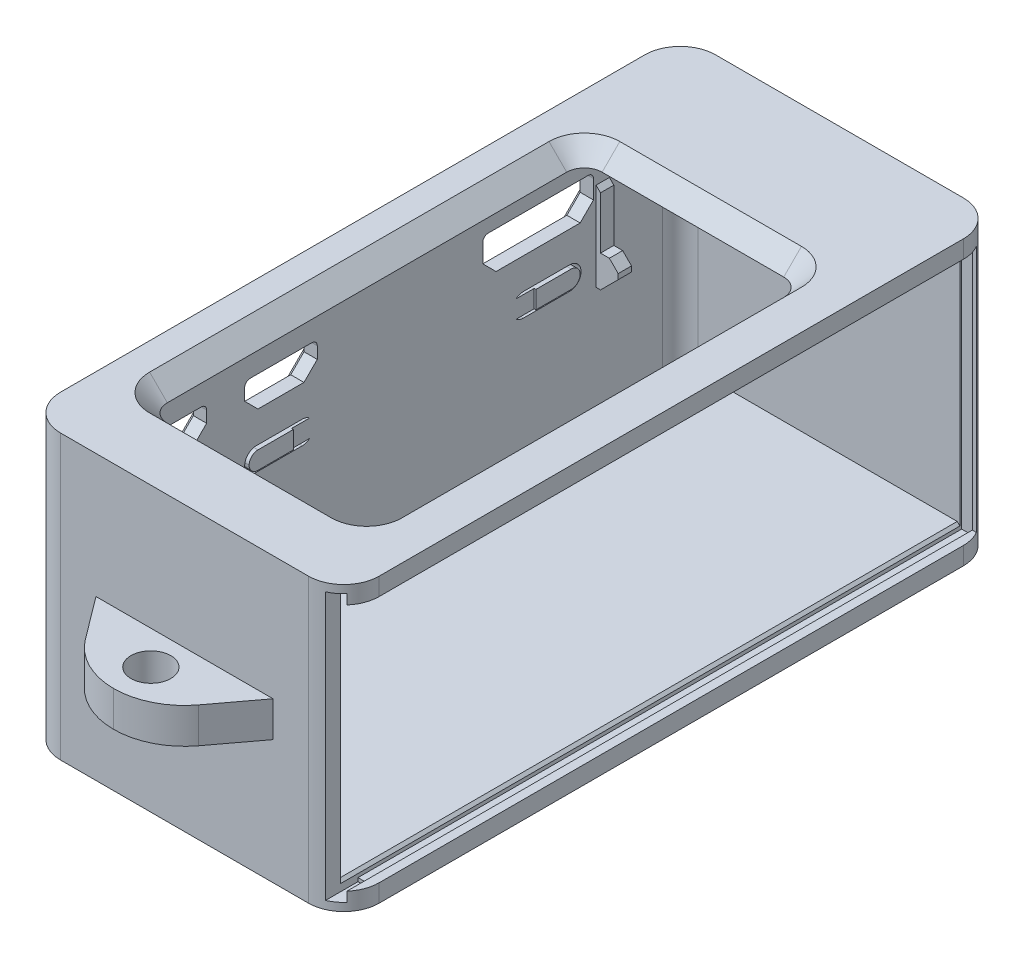
SolidWorks part; units mm, degrees
ref_plane "前视基准面" through (0, 0, 0) normal (0, 0, 1) x (1, 0, 0)
ref_plane "上视基准面" through (0, 0, 0) normal (0, 1, 0) x (1, 0, 0)
ref_plane "右视基准面" through (0, 0, 0) normal (1, 0, 0) x (0, 0, -1)
sketch "草图1" plane through (0, 0, 0) normal (1, 0, 0) x (0, 0, -1)
  line L1 (-54.0501, 29.0398) -> (19.9499, 29.0398)
  line L2 (-54.0501, 29.0398) -> (-54.0501, -2.9602)
  line L3 (-54.0501, -2.9602) -> (19.9499, -2.9602)
  line L4 (19.9499, 29.0398) -> (19.9499, -2.9602)
  dimension "D1" = 74
  dimension "D2" = 32
extrude "凸台-拉伸1" add sketch "草图1" along normal blind 36
sketch "草图2" plane through (36, 0, 0) normal (1, 0, 0) x (0, 0, -1)
  line L8 (17.9499, -0.9602) -> (17.9499, 27.0398)
  line L9 (-52.0501, -0.9602) -> (17.9499, -0.9602)
  line L10 (-52.0501, 27.0398) -> (-52.0501, -0.9602)
  line L11 (17.9499, 27.0398) -> (-52.0501, 27.0398)
  line L12 (17.9499, -0.9602) -> (17.9499, 27.0398)
  line L13 (-52.0501, -0.9602) -> (17.9499, -0.9602)
  line L14 (-52.0501, 27.0398) -> (-52.0501, -0.9602)
  line L15 (17.9499, 27.0398) -> (-52.0501, 27.0398)
  dimension "D1" = 2
extrude "切除-拉伸1" cut sketch "草图2" against normal blind 34
fillet "圆角1" radius 2 2 edges at (2, 13.0398, -17.9499) (2, 13.0398, 52.0501)
fillet "圆角2" radius 4 4 edges at (0, 13.0398, -19.9499) (0, 13.0398, 54.0501) (36, 13.0398, 54.0501) (36, 13.0398, -19.9499)
sketch "草图3" plane through (0, 29.0398, 0) normal (0, 1, 0) x (1, 0, 0)
  line L0 (32, 19.9499) -> (4, 19.9499) construction
  line L1 (29.59, 4.0599) -> (5.07, 4.0599)
  line L2 (29.59, 4.0599) -> (29.59, -45.0601)
  line L3 (29.59, -45.0601) -> (5.07, -45.0601)
  line L4 (5.07, 4.0599) -> (5.07, -45.0601)
  line L5 (36, 15.9499) -> (36, -50.0501) construction
  line L6 (32, -54.0501) -> (4, -54.0501) construction
  line L7 (0, 15.9499) -> (0, -50.0501) construction
  dimension "D1" = 15.89
  dimension "D2" = 6.41
  dimension "D3" = 8.99
  dimension "D4" = 5.07
extrude "切除-拉伸2" cut sketch "草图3" against normal blind 10
fillet "圆角3" radius 2 4 edges at (5.07, 28.0398, 45.0601) (29.59, 28.0398, 45.0601) (29.59, 28.0398, -4.0599) (5.07, 28.0398, -4.0599)
chamfer "倒角1" distance 2 angle 45 8 edges at (17.33, 29.0398, 45.0601) (29.0042, 29.0398, 44.4744) (5.6558, 29.0398, 44.4744) (29.59, 29.0398, 20.5001) (5.07, 29.0398, 20.5001) (29.0042, 29.0398, -3.4741) (5.6558, 29.0398, -3.4741) (17.33, 29.0398, -4.0599)
sketch "草图4" plane through (0, 0, 0) normal (-1, 0, 0) x (0, 0, 1)
  line L0 (-15.9499, 29.0398) -> (50.0501, 29.0398) construction
  line L1 (-8.1499, 22.4398) -> (4.3501, 22.4398)
  line L2 (-8.1499, 22.4398) -> (-8.1499, 18.2398)
  line L3 (-8.1499, 18.2398) -> (4.3501, 18.2398)
  line L4 (4.3501, 22.4398) -> (4.3501, 18.2398)
  line L5 (23.0501, 21.6812) -> (31.2501, 21.6812)
  line L6 (23.0501, 21.6812) -> (23.0501, 18.2398)
  line L7 (23.0501, 18.2398) -> (31.2501, 18.2398)
  line L8 (31.2501, 21.6812) -> (31.2501, 18.2398)
  line L9 (35.5501, 21.6398) -> (43.7501, 21.6398)
  line L10 (35.5501, 21.6398) -> (35.5501, 18.2398)
  line L11 (35.5501, 18.2398) -> (43.7501, 18.2398)
  line L12 (43.7501, 21.6398) -> (43.7501, 18.2398)
  line L13 (-6.7499, 14.7398) -> (1.0501, 14.7398)
  line L14 (-6.7499, 14.7398) -> (-6.7499, 12.1398)
  line L15 (-6.7499, 12.1398) -> (1.0501, 12.1398)
  line L16 (1.0501, 14.7398) -> (1.0501, 12.1398)
  line L17 (23.4501, 14.7398) -> (31.2501, 14.7398)
  line L18 (23.4501, 14.7398) -> (23.4501, 12.1398)
  line L19 (23.4501, 12.1398) -> (31.2501, 12.1398)
  line L20 (31.2501, 14.7398) -> (31.2501, 12.1398)
  line L21 (33.8696, 14.7398) -> (43.3696, 14.7398)
  line L22 (33.8696, 14.7398) -> (33.8696, 11.5398)
  line L23 (33.8696, 11.5398) -> (43.3696, 11.5398)
  line L24 (43.3696, 14.7398) -> (43.3696, 11.5398)
  line L25 (54.0501, 29.0398) -> (54.0501, -2.9602) construction
  point P24 (0, 0)
  point P27 (0, 0)
  point P28 (0, 0)
  point P31 (0, 0)
  point P32 (0, 0)
  dimension "D1" = 14.3
  dimension "D2" = 3.2
  dimension "D3" = 2.6
  dimension "D4" = 7.8
  dimension "D5" = 7.8
  dimension "D6" = 8.2
  dimension "D7" = 8.2
  dimension "D8" = 3.4
  dimension "D9" = 12.5
  dimension "D10" = 4.2
  dimension "D11" = 10.8
  dimension "D12" = 10.3
  dimension "D13" = 4.3
  dimension "D14" = 18.7
  dimension "D15" = 9.5
  dimension "D16" = 53
extrude "切除-拉伸3" cut sketch "草图4" against normal blind 10
sketch "草图5" plane through (2, 0, 0) normal (1, 0, 0) x (0, 0, -1)
  line L0 (-23.4501, 12.1398) -> (-23.4501, 14.7398) construction
  line L1 (-23.4501, 14.4398) -> (-30.9501, 14.4398)
  line L2 (-23.4501, 14.4398) -> (-23.4501, 12.4398)
  line L3 (-23.4501, 12.4398) -> (-30.9501, 12.4398)
  line L4 (-30.9501, 14.4398) -> (-30.9501, 12.4398)
  line L5 (-1.0501, 14.7398) -> (-1.0501, 12.1398) construction
  line L6 (-1.0501, 12.4398) -> (6.4499, 12.4398)
  line L7 (-1.0501, 12.4398) -> (-1.0501, 14.4398)
  line L8 (-1.0501, 14.4398) -> (6.4499, 14.4398)
  line L9 (6.4499, 12.4398) -> (6.4499, 14.4398)
  line L10 (-23.4501, 14.7398) -> (-31.2501, 14.7398) construction
  line L11 (-31.2501, 12.1398) -> (-23.4501, 12.1398) construction
  line L12 (-31.2501, 14.7398) -> (-31.2501, 12.1398) construction
  line L13 (6.7499, 14.7398) -> (-1.0501, 14.7398) construction
  line L14 (-1.0501, 12.1398) -> (6.7499, 12.1398) construction
  line L15 (6.7499, 12.1398) -> (6.7499, 14.7398) construction
  dimension "D1" = 0.3
  dimension "D2" = 0.3
  dimension "D3" = 0.3
  dimension "D4" = 0.3
  dimension "D5" = 0.3
  dimension "D6" = 0.3
extrude "凸台-拉伸2" add sketch "草图5" against normal blind 1.2
sketch "草图6" plane through (0.8, 0, 0) normal (-1, 0, 0) x (0, 0, 1)
  line L0 (1.0501, 12.4398) -> (-6.4499, 12.4398) construction
  line L1 (-6.4499, 14.4398) -> (-1.4499, 14.4398)
  line L2 (-6.4499, 14.4398) -> (-6.4499, 12.4398)
  line L3 (-6.4499, 12.4398) -> (-1.4499, 12.4398)
  line L4 (-1.4499, 14.4398) -> (-1.4499, 12.4398)
  line L5 (30.9501, 12.4398) -> (23.4501, 12.4398) construction
  line L6 (30.9501, 14.4398) -> (25.9501, 14.4398)
  line L7 (30.9501, 14.4398) -> (30.9501, 12.4398)
  line L8 (30.9501, 12.4398) -> (25.9501, 12.4398)
  line L9 (25.9501, 14.4398) -> (25.9501, 12.4398)
  dimension "D1" = 5
  dimension "D2" = 5
extrude "凸台-拉伸3" add sketch "草图6" along normal blind 1.5 and the other way blind 1.4
fillet "圆角4" radius 0.6 10 edges at (1, 11.5398, 33.8696) (1, 14.7398, 33.8696) (1, 14.7398, 43.3696) (1, 11.5398, 43.3696) (1, 21.6398, 35.5501) (1, 21.6398, 43.7501) (1, 21.6812, 31.2501) (1, 21.6812, 23.0501) (1, 22.4398, -8.1499) (1, 22.4398, 4.3501)
chamfer "倒角2" distance 1.5 angle 45 6 edges at (1, 18.2398, 43.7501) (1, 18.2398, 35.5501) (1, 18.2398, 31.2501) (1, 18.2398, 23.0501) (1, 18.2398, 4.3501) (1, 18.2398, -8.1499)
fillet "圆角5" radius 1 8 edges at (0.05, 12.4398, 25.9501) (0.05, 14.4398, 25.9501) (0.75, 12.4398, 30.9501) (0.75, 14.4398, 30.9501) (0.05, 12.4398, -1.4499) (0.05, 14.4398, -1.4499) (0.75, 12.4398, -6.4499) (0.75, 14.4398, -6.4499)
chamfer "倒角10" distance 0.2 angle 45 12 edges at (-0.7, 12.4398, 28.4501) (-0.7, 12.7327, 30.6572) (-0.7, 12.7327, 26.243) (-0.7, 14.1469, 30.6572) (-0.7, 14.1469, 26.243) (-0.7, 14.4398, 28.4501) (-0.7, 12.4398, -3.9499) (-0.7, 12.7327, -1.7428) (-0.7, 12.7327, -6.157) (-0.7, 14.1469, -1.7428) (-0.7, 14.1469, -6.157) (-0.7, 14.4398, -3.9499)
fillet "圆角6" radius 1.3 8 edges at (1, 14.7398, 1.0501) (1, 12.1398, 1.0501) (1, 12.1398, -6.7499) (1, 14.7398, -6.7499) (1, 14.7398, 23.4501) (1, 12.1398, 23.4501) (1, 12.1398, 31.2501) (1, 14.7398, 31.2501)
chamfer "倒角4" distance 0.5 angle 45 44 edges at (0, 12.1398, -2.8499) (0, 12.5206, 0.6694) (0, 12.5206, -6.3691) (0, 14.359, 0.6694) (0, 14.359, -6.3691) (0, 14.7398, -2.8499) (0, 18.9898, -7.3999) (0, 18.2398, -1.8999) (0, 18.9898, 3.6001) (0, 20.7898, 4.3501) (0, 20.7898, -8.1499) (0, 22.2641, 4.1744) (0, 22.2641, -7.9741) (0, 22.4398, -1.8999) (0, 11.5398, 38.6196) (0, 11.7155, 43.1938) (0, 11.7155, 34.0453) (0, 13.1398, 43.3696) (0, 13.1398, 33.8696) (0, 14.5641, 43.1938) (0, 14.5641, 34.0453) (0, 14.7398, 38.6196) (0, 12.1398, 27.3501) (0, 12.5206, 30.8694) (0, 12.5206, 23.8309) (0, 14.359, 30.8694) (0, 14.359, 23.8309) (0, 14.7398, 27.3501) (0, 20.4105, 23.0501) (0, 21.5055, 23.2259) (0, 21.6812, 27.1501) (0, 21.5055, 31.0744) (0, 18.9898, 23.8001) (0, 18.2398, 27.1501) (0, 18.9898, 30.5001) (0, 20.4105, 31.2501) (0, 18.9898, 43.0001) (0, 18.2398, 39.6501) (0, 18.9898, 36.3001) (0, 20.3898, 35.5501) (0, 21.4641, 35.7259) (0, 21.6398, 39.6501) (0, 20.3898, 43.7501) (0, 21.4641, 43.5744)
sketch "草图7" plane through (2, 0, 0) normal (1, 0, 0) x (0, 0, -1)
  line L0 (15.9499, 27.0398) -> (-50.0501, 27.0398) construction
  line L1 (-46.0501, 21.0398) -> (-44.5501, 21.0398)
  line L2 (-46.0501, 21.0398) -> (-46.0501, 11.0398)
  line L3 (-46.0501, 11.0398) -> (-44.5501, 11.0398)
  line L4 (-44.5501, 21.0398) -> (-44.5501, 11.0398)
  line L5 (8.4499, 21.0398) -> (9.9499, 21.0398)
  line L6 (8.4499, 21.0398) -> (8.4499, 11.0398)
  line L7 (8.4499, 11.0398) -> (9.9499, 11.0398)
  line L8 (9.9499, 21.0398) -> (9.9499, 11.0398)
  line L11 (17.9499, -0.9602) -> (17.9499, 27.0398) construction
  line L12 (-52.0501, 27.0398) -> (-52.0501, -0.9602) construction
  point P10 (0, 0)
  point P11 (0, 0)
  dimension "D1" = 6
  dimension "D2" = 10
  dimension "D3" = 1.5
  dimension "D4" = 1.5
  dimension "D5" = 8
  dimension "D6" = 6
extrude "凸台-拉伸4" add sketch "草图7" along normal blind 0.5
sketch "草图10" plane through (2.5, 0, 0) normal (1, 0, 0) x (0, 0, -1)
  line L1 (-46.0501, 11.0398) -> (-44.5501, 11.0398)
  line L2 (-46.0501, 11.0398) -> (-46.0501, 14.6398)
  line L3 (-46.0501, 14.6398) -> (-44.5501, 14.6398)
  line L4 (-44.5501, 11.0398) -> (-44.5501, 14.6398)
  line L7 (8.4499, 11.0398) -> (9.9499, 11.0398)
  line L8 (8.4499, 11.0398) -> (8.4499, 14.6398)
  line L9 (8.4499, 14.6398) -> (9.9499, 14.6398)
  line L10 (9.9499, 11.0398) -> (9.9499, 14.6398)
  point P5 (0, 0)
  dimension "D1" = 3.6
extrude "凸台-拉伸6" add sketch "草图10" along normal blind 2
chamfer "倒角7" distance 1 angle 45 2 edges at (4.5, 14.6398, -9.1999) (4.5, 14.6398, 45.3001)
chamfer "倒角8" distance 2 angle 45 2 edges at (4.5, 11.0398, 45.3001) (4.5, 11.0398, -9.1999)
chamfer "倒角5" distance 0.5 angle 45 2 edges at (2.5, 21.0398, 45.3001) (2.5, 21.0398, -9.1999)
sketch "草图8" plane through (2, 0, 0) normal (1, 0, 0) x (0, 0, -1)
  line L1 (-52.0501, 22.2398) -> (-48.0501, 22.2398)
  line L2 (-52.0501, 22.2398) -> (-52.0501, 24.2398)
  line L3 (-52.0501, 24.2398) -> (-48.0501, 24.2398)
  line L4 (-48.0501, 22.2398) -> (-48.0501, 24.2398)
  line L6 (17.9499, 24.2398) -> (11.9499, 24.2398)
  line L7 (17.9499, 24.2398) -> (17.9499, 22.2398)
  line L8 (17.9499, 22.2398) -> (11.9499, 22.2398)
  line L9 (11.9499, 24.2398) -> (11.9499, 22.2398)
  line L10 (15.9499, 27.0398) -> (-50.0501, 27.0398) construction
  line L11 (17.9499, -0.9602) -> (17.9499, 27.0398) construction
  line L12 (-52.0501, 27.0398) -> (-52.0501, -0.9602) construction
  point P4 (0, 0)
  point P10 (0, 0)
  point P14 (0, 0)
  point P15 (0, 0)
  dimension "D1" = 2.8
  dimension "D2" = 2
  dimension "D3" = 4
  dimension "D4" = 6
extrude "凸台-拉伸5" add sketch "草图8" along normal blind 3
chamfer "倒角6" distance 1 angle 45 2 edges at (5, 24.2398, -14.9499) (5, 24.2398, 50.0501)
sketch "草图12" plane through (0, 0, 54.0501) normal (0, 0, 1) x (1, 0, 0)
  line L0 (4, -0.9602) -> (35.4641, -0.9602) construction
  line L1 (36, 27.0398) -> (33.6, 27.0398)
  line L2 (36, 27.0398) -> (36, -0.9602)
  line L3 (36, -0.9602) -> (33.6, -0.9602)
  line L4 (33.6, 27.0398) -> (33.6, -0.9602)
  dimension "D1" = 2.4
extrude "切除-拉伸5" cut sketch "草图12" against normal blind 10.8
sketch "草图11" plane through (0, -0.9602, 0) normal (0, 1, 0) x (1, 0, 0)
  line L0 (32, 19.9499) -> (4, 19.9499) construction
  line L1 (35, 17.9499) -> (33.6, 17.9499)
  line L2 (35, 17.9499) -> (35, -54.0501)
  line L3 (35, -54.0501) -> (33.6, -54.0501)
  line L4 (33.6, 17.9499) -> (33.6, -54.0501)
  line L5 (32, -54.0501) -> (4, -54.0501) construction
  line L6 (36, -50.0501) -> (36, 15.9499) construction
  point P4 (32.2958, 15.4883)
  point P5 (0, 0)
  point P6 (31.5468, 17.1155)
  dimension "D1" = 2
  dimension "D2" = 0
  dimension "D3" = 1
  dimension "D4" = 1.4
extrude "切除-拉伸4" cut sketch "草图11" against normal blind 0.7
sketch "草图13" plane through (0, 27.0398, 0) normal (0, -1, 0) x (1, 0, 0)
  line L10 (33.6, -17.9499) -> (35, -17.9499)
  line L11 (33.6, 54.0501) -> (33.6, -17.9499)
  line L12 (35, 54.0501) -> (33.6, 54.0501)
  line L13 (35, -17.9499) -> (35, 54.0501)
  line L14 (33.6, -17.9499) -> (35, -17.9499)
  line L15 (33.6, 54.0501) -> (33.6, -17.9499)
  line L16 (35, 54.0501) -> (33.6, 54.0501)
  line L17 (35, -17.9499) -> (35, 54.0501)
  dimension "D1" = 0
extrude "切除-拉伸6" cut sketch "草图13" against normal blind 0.7
sketch "草图14" plane through (0, -1.6602, 0) normal (0, 1, 0) x (1, 0, 0)
  line L1 (33.6, -54.0501) -> (35, -54.0501)
  line L2 (33.6, -54.0501) -> (33.6, -50.0501)
  line L3 (33.6, -50.0501) -> (35, -50.0501)
  line L4 (35, -54.0501) -> (35, -50.0501)
  line L5 (32, -54.0501) -> (4, -54.0501) construction
  line L6 (33.6, -53.7162) -> (33.6, 17.9499) construction
  point P5 (0, 0)
  point P8 (0, 0)
  point P11 (0, 0)
  dimension "D1" = 4
extrude "切除-拉伸7" cut sketch "草图14" against normal blind 0.4
sketch "草图15" plane through (0, 27.7398, 0) normal (0, -1, 0) x (1, 0, 0)
  line L3 (35, 50.0501) -> (35, 52.6959)
  line L4 (33.6, 50.0501) -> (35, 50.0501)
  line L5 (33.6, 53.7162) -> (33.6, 50.0501)
  line L7 (33.6, 50.0501) -> (35, 50.0501)
  line L8 (33.6, 53.7162) -> (33.6, 50.0501)
  line L10 (35, 50.0501) -> (35, 52.6959)
  arc A1 (35, 52.6959) -> (33.6, 53.7162) centre (32, 50.0501) ccw
  arc A2 (35, 52.6959) -> (33.6, 53.7162) centre (32, 50.0501) ccw
  dimension "D1" = 0
extrude "切除-拉伸8" cut sketch "草图15" against normal blind 0.4
sketch "草图16" plane through (0, 0, -17.9499) normal (0, 0, 1) x (1, 0, 0)
  line L0 (33.6, 28.1398) -> (33.6, -2.0602) construction
  line L1 (33.6, 27.7398) -> (35, 27.7398)
  line L2 (33.6, 27.7398) -> (33.6, -1.6602)
  line L3 (33.6, -1.6602) -> (35, -1.6602)
  line L4 (35, 27.7398) -> (35, -1.6602)
  point P6 (35, -1.7602)
  point P8 (33, 27.8398)
  point P10 (0, 0)
  point P11 (35, 27.7398)
  point P13 (33.6, 27.7398)
  point P16 (35, -1.6602)
extrude "切除-拉伸9" cut sketch "草图16" against normal blind 0.2
chamfer "倒角9" distance 0.3 angle 45 2 edges at (33.6, 27.0398, 17.0501) (33.6, -0.9602, 17.0501)
ref_plane "基准面4" through (0, 13.0398, 0) normal (0, -1, 0) x (-1, 0, 0)
sketch "草图17" plane through (0, 13.0398, 0) normal (0, -1, 0) x (-1, 0, 0)
  line L0 (-28, -54.0501) -> (-8, -54.0501)
  line L1 (-32, -54.0501) -> (-4, -54.0501) construction
  line L2 (-8, -54.0501) -> (-14, -62.0501)
  line L3 (-14, -62.0501) -> (-22, -62.0501)
  line L4 (-22, -62.0501) -> (-28, -54.0501)
  line L5 (0, -50.0501) -> (0, 15.9499) construction
  line L7 (-36, -50.0501) -> (-36, 15.9499) construction
  dimension "D1" = 8
  dimension "D2" = 14
  dimension "D3" = 8
  dimension "D4" = 14
  dimension "D5" = 8
extrude "凸台-拉伸7" add sketch "草图17" along normal blind 2 and the other way blind 2
fillet "圆角7" radius 8 2 edges at (14, 13.0398, 62.0501) (22, 13.0398, 62.0501)
sketch "草图18" plane through (0, 11.0398, 0) normal (0, -1, 0) x (1, 0, 0)
  line L0 (18, 53.5945) -> (18, 54.5066) construction
  line L2 (32, 54.0501) -> (4, 54.0501) construction
  circle A0 centre (18, 57.8501) radius 2.25
  point P3 (18, 58.3057)
  dimension "D2" = 4.5
  dimension "D1" = 3.8
extrude "切除-拉伸10" cut sketch "草图18" against normal through all
